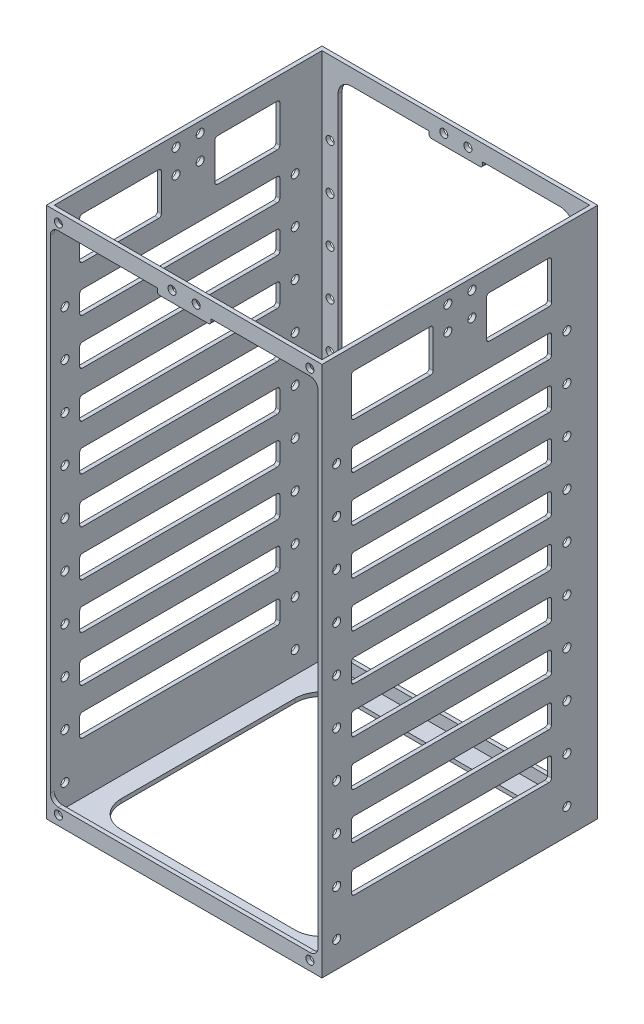
SolidWorks part; units mm, degrees
ref_plane "Front Plane" through (0, 0, 0) normal (0, 0, 1) x (1, 0, 0)
ref_plane "Top Plane" through (0, 0, 0) normal (0, 1, 0) x (1, 0, 0)
ref_plane "Right Plane" through (0, 0, 0) normal (1, 0, 0) x (0, 0, -1)
sketch "Sketch1" plane through (0, 0, 0) normal (0, 1, 0) x (1, 0, 0)
  line L1 (-51.5, -51.5) -> (51.5, -51.5)
  line L2 (-51.5, -51.5) -> (-51.5, 51.5)
  line L3 (-51.5, 51.5) -> (51.5, 51.5)
  line L4 (51.5, -51.5) -> (51.5, 51.5)
  line L5 (-51.5, -51.5) -> (51.5, 51.5) construction
  line L6 (-51.5, 51.5) -> (51.5, -51.5) construction
  line L7 (-32.5, -42.5) -> (32.5, -42.5)
  line L8 (-42.5, -32.5) -> (-42.5, 32.5)
  line L9 (-32.5, 42.5) -> (32.5, 42.5)
  line L10 (42.5, -32.5) -> (42.5, 32.5)
  line L11 (-42.5, -42.5) -> (42.5, 42.5) construction
  line L12 (-42.5, 42.5) -> (42.5, -42.5) construction
  arc A0 (32.5, -42.5) -> (42.5, -32.5) centre (32.5, -32.5) ccw
  arc A1 (32.5, 42.5) -> (42.5, 32.5) centre (32.5, 32.5) cw
  arc A2 (-42.5, 32.5) -> (-32.5, 42.5) centre (-32.5, 32.5) cw
  arc A3 (-32.5, -42.5) -> (-42.5, -32.5) centre (-32.5, -32.5) cw
  point P0 (0, 0)
  point P6 (0, 0)
  dimension "D3" = 10
  dimension "D1" = 103
  dimension "D2" = 42.5
extrude "Boss-Extrude2" add sketch "Sketch1" along normal blind 1.5 contours A3 L7 A0 L10 A1 L9 A2 L8 | L2 L1 L4 L3 region at (0, 0, 0)
sketch "Sketch3" plane through (0, 1.5, 0) normal (0, 1, 0) x (1, 0, 0)
  line L1 (-51.5, -51.5) -> (51.5, -51.5)
  line L2 (-51.5, -51.5) -> (-51.5, 51.5)
  line L3 (-51.5, 51.5) -> (51.5, 51.5)
  line L4 (51.5, -51.5) -> (51.5, 51.5)
  line L5 (-51.5, -51.5) -> (51.5, 51.5) construction
  line L6 (-51.5, 51.5) -> (51.5, -51.5) construction
  line L7 (-50, -50) -> (50, -50)
  line L8 (-50, -50) -> (-50, 50)
  line L9 (-50, 50) -> (50, 50)
  line L10 (50, -50) -> (50, 50)
  line L11 (-50, -50) -> (50, 50) construction
  line L12 (-50, 50) -> (50, -50) construction
  point P0 (0, 0)
  point P7 (0, 0)
  dimension "D1" = 100
extrude "Boss-Extrude3" add sketch "Sketch3" along normal blind 197 contours L8 L7 L10 L9 | L2 L3 L4 L1
sketch "Sketch4" plane through (0, 0, -51.5) normal (0, 0, 1) x (1, 0, 0)
  line L0 (-51.5, 0) -> (51.5, 0) construction
  line L1 (-39, 6) -> (39, 6)
  line L2 (-44, 11) -> (-44, 187.5)
  line L3 (-39, 192.5) -> (39, 192.5)
  line L4 (44, 11) -> (44, 187.5)
  line L5 (-44, 6) -> (44, 192.5) construction
  line L6 (-44, 192.5) -> (44, 6) construction
  line L7 (51.5, 198.5) -> (51.5, 0) construction
  line L8 (-50, 198.5) -> (50, 198.5) construction
  line L9 (-51.5, 198.5) -> (-51.5, 0) construction
  arc A0 (-39, 6) -> (-44, 11) centre (-39, 11) cw
  arc A1 (39, 6) -> (44, 11) centre (39, 11) ccw
  arc A2 (39, 192.5) -> (44, 187.5) centre (39, 187.5) cw
  arc A3 (-44, 187.5) -> (-39, 192.5) centre (-39, 187.5) cw
  point P0 (0, 99.25)
  dimension "D5" = 5
  dimension "D1" = 6
  dimension "D2" = 7.5
  dimension "D3" = 6
  dimension "D4" = 7.5
extrude "Cut-Extrude1" cut sketch "Sketch4" along normal up to surface (1.5 mm away) up to face at (0, 100, -50)
sketch "Sketch5" plane through (0, 0, 51.5) normal (0, 0, 1) x (1, 0, 0)
  line L0 (-51.5, 198.5) -> (51.5, 198.5) construction
  line L1 (-47, 6) -> (47, 6)
  line L2 (-50, 9) -> (-50, 189.5)
  line L3 (-47, 192.5) -> (47, 192.5)
  line L4 (50, 9) -> (50, 189.5)
  line L5 (-50, 6) -> (50, 192.5) construction
  line L6 (-50, 192.5) -> (50, 6) construction
  line L7 (-51.5, 1.5) -> (51.5, 1.5) construction
  line L8 (-51.5, 198.5) -> (-51.5, 0) construction
  line L9 (51.5, 198.5) -> (51.5, 0) construction
  arc A0 (47, 6) -> (50, 9) centre (47, 9) ccw
  arc A1 (-47, 6) -> (-50, 9) centre (-47, 9) cw
  arc A2 (47, 192.5) -> (50, 189.5) centre (47, 189.5) cw
  arc A3 (-50, 189.5) -> (-47, 192.5) centre (-47, 189.5) cw
  point P0 (0, 99.25)
  dimension "D5" = 3
  dimension "D1" = 6
  dimension "D2" = 4.5
  dimension "D3" = 1.5
  dimension "D4" = 1.5
sketch "Sketch6" plane through (51.5, 0, 0) normal (1, 0, 0) x (0, 0, -1)
  line L0 (-51.5, 6) -> (-51.5, 192.5) construction
  line L2 (-51.5, 0) -> (51.5, 0) construction
  circle A0 centre (-46, 9.75) radius 1.5
  circle A1 centre (40, 9.75) radius 1.5
  circle A2 centre (-46, 26.85) radius 1.5
  circle A3 centre (40, 26.85) radius 1.5
  circle A4 centre (-46, 43.95) radius 1.5
  circle A5 centre (40, 43.95) radius 1.5
  circle A6 centre (-46, 61.05) radius 1.5
  circle A7 centre (40, 61.05) radius 1.5
  circle A8 centre (-46, 78.15) radius 1.5
  circle A9 centre (40, 78.15) radius 1.5
  circle A10 centre (-46, 95.25) radius 1.5
  circle A11 centre (40, 95.25) radius 1.5
  circle A12 centre (-46, 112.35) radius 1.5
  circle A13 centre (40, 112.35) radius 1.5
  circle A14 centre (-46, 129.45) radius 1.5
  circle A15 centre (40, 129.45) radius 1.5
  circle A16 centre (-46, 146.55) radius 1.5
  circle A17 centre (40, 146.55) radius 1.5
  circle A18 centre (-46, 163.65) radius 1.5
  circle A19 centre (40, 163.65) radius 1.5
  dimension "D4" = 3
  dimension "D5" = 3
  dimension "D1" = 5.5
  dimension "D2" = 86
  dimension "D3" = 9.75
  dimension "D7" = 17.1
  dimension "D9" = 17.1
  dimension "D6" = 9
  dimension "D8" = 2
extrude "Cut-Extrude2" cut sketch "Sketch6" against normal through all
extrude "Cut-Extrude3" cut sketch "Sketch5" against normal up to surface (1.5 mm away) up to face at (0, 100, 50)
sketch "Sketch7" plane through (51.5, 0, 0) normal (1, 0, 0) x (0, 0, -1)
  line L0 (-40.5, 38.95) -> (-40.5, 45.45)
  line L1 (-39.5, 20.85) -> (33.25, 20.85)
  line L2 (-40.5, 21.85) -> (-40.5, 28.35)
  line L3 (-39.5, 29.35) -> (33.25, 29.35)
  line L4 (34.25, 21.85) -> (34.25, 28.35)
  line L5 (-40.5, 20.85) -> (34.25, 29.35) construction
  line L6 (-40.5, 29.35) -> (34.25, 20.85) construction
  line L7 (-40.5, 158.65) -> (-40.5, 165.15)
  line L8 (-39.5, 37.95) -> (33.25, 37.95)
  line L9 (34.25, 38.95) -> (34.25, 45.45)
  line L10 (-39.5, 46.45) -> (33.25, 46.45)
  line L11 (-40.5, 56.05) -> (-40.5, 62.55)
  line L12 (-39.5, 55.05) -> (33.25, 55.05)
  line L13 (34.25, 56.05) -> (34.25, 62.55)
  line L14 (-39.5, 63.55) -> (33.25, 63.55)
  line L15 (-40.5, 73.15) -> (-40.5, 79.65)
  line L16 (-39.5, 72.15) -> (33.25, 72.15)
  line L17 (34.25, 73.15) -> (34.25, 79.65)
  line L18 (-39.5, 80.65) -> (33.25, 80.65)
  line L19 (-40.5, 90.25) -> (-40.5, 96.75)
  line L20 (-39.5, 89.25) -> (33.25, 89.25)
  line L21 (34.25, 90.25) -> (34.25, 96.75)
  line L22 (-39.5, 97.75) -> (33.25, 97.75)
  line L23 (-40.5, 107.35) -> (-40.5, 113.85)
  line L24 (-39.5, 106.35) -> (33.25, 106.35)
  line L25 (34.25, 107.35) -> (34.25, 113.85)
  line L26 (-39.5, 114.85) -> (33.25, 114.85)
  line L27 (-40.5, 124.45) -> (-40.5, 130.95)
  line L28 (-39.5, 123.45) -> (33.25, 123.45)
  line L29 (34.25, 124.45) -> (34.25, 130.95)
  line L30 (-39.5, 131.95) -> (33.25, 131.95)
  line L31 (-40.5, 141.55) -> (-40.5, 148.05)
  line L32 (-39.5, 140.55) -> (33.25, 140.55)
  line L33 (34.25, 141.55) -> (34.25, 148.05)
  line L34 (-39.5, 149.05) -> (33.25, 149.05)
  line L35 (-39.5, 157.65) -> (33.25, 157.65)
  line L36 (34.25, 158.65) -> (34.25, 165.15)
  line L37 (-39.5, 166.15) -> (33.25, 166.15)
  line L38 (-40.5, 141.55) -> (-40.5, 158.65) construction
  circle A0 centre (-46, 9.75) radius 1.5 construction
  arc A1 (33.25, 29.35) -> (34.25, 28.35) centre (33.25, 28.35) cw
  arc A2 (33.25, 20.85) -> (34.25, 21.85) centre (33.25, 21.85) ccw
  arc A3 (-39.5, 20.85) -> (-40.5, 21.85) centre (-39.5, 21.85) cw
  arc A4 (-40.5, 28.35) -> (-39.5, 29.35) centre (-39.5, 28.35) cw
  arc A5 (-40.5, 45.45) -> (-39.5, 46.45) centre (-39.5, 45.45) cw
  arc A6 (-39.5, 37.95) -> (-40.5, 38.95) centre (-39.5, 38.95) cw
  arc A7 (33.25, 37.95) -> (34.25, 38.95) centre (33.25, 38.95) ccw
  arc A8 (33.25, 46.45) -> (34.25, 45.45) centre (33.25, 45.45) cw
  arc A9 (-40.5, 62.55) -> (-39.5, 63.55) centre (-39.5, 62.55) cw
  arc A10 (-39.5, 55.05) -> (-40.5, 56.05) centre (-39.5, 56.05) cw
  arc A11 (33.25, 55.05) -> (34.25, 56.05) centre (33.25, 56.05) ccw
  arc A12 (33.25, 63.55) -> (34.25, 62.55) centre (33.25, 62.55) cw
  arc A13 (-40.5, 79.65) -> (-39.5, 80.65) centre (-39.5, 79.65) cw
  arc A14 (-39.5, 72.15) -> (-40.5, 73.15) centre (-39.5, 73.15) cw
  arc A15 (33.25, 72.15) -> (34.25, 73.15) centre (33.25, 73.15) ccw
  arc A16 (33.25, 80.65) -> (34.25, 79.65) centre (33.25, 79.65) cw
  arc A17 (-40.5, 96.75) -> (-39.5, 97.75) centre (-39.5, 96.75) cw
  arc A18 (-39.5, 89.25) -> (-40.5, 90.25) centre (-39.5, 90.25) cw
  arc A19 (33.25, 89.25) -> (34.25, 90.25) centre (33.25, 90.25) ccw
  arc A20 (33.25, 97.75) -> (34.25, 96.75) centre (33.25, 96.75) cw
  arc A21 (-40.5, 113.85) -> (-39.5, 114.85) centre (-39.5, 113.85) cw
  arc A22 (-39.5, 106.35) -> (-40.5, 107.35) centre (-39.5, 107.35) cw
  arc A23 (33.25, 106.35) -> (34.25, 107.35) centre (33.25, 107.35) ccw
  arc A24 (33.25, 114.85) -> (34.25, 113.85) centre (33.25, 113.85) cw
  arc A25 (-40.5, 130.95) -> (-39.5, 131.95) centre (-39.5, 130.95) cw
  arc A26 (-39.5, 123.45) -> (-40.5, 124.45) centre (-39.5, 124.45) cw
  arc A27 (33.25, 123.45) -> (34.25, 124.45) centre (33.25, 124.45) ccw
  arc A28 (33.25, 131.95) -> (34.25, 130.95) centre (33.25, 130.95) cw
  arc A29 (-40.5, 148.05) -> (-39.5, 149.05) centre (-39.5, 148.05) cw
  arc A30 (-39.5, 140.55) -> (-40.5, 141.55) centre (-39.5, 141.55) cw
  arc A31 (33.25, 140.55) -> (34.25, 141.55) centre (33.25, 141.55) ccw
  arc A32 (33.25, 149.05) -> (34.25, 148.05) centre (33.25, 148.05) cw
  arc A33 (-40.5, 165.15) -> (-39.5, 166.15) centre (-39.5, 165.15) cw
  arc A34 (-39.5, 157.65) -> (-40.5, 158.65) centre (-39.5, 158.65) cw
  circle A35 centre (40, 9.75) radius 1.5 construction
  arc A36 (33.25, 157.65) -> (34.25, 158.65) centre (33.25, 158.65) ccw
  arc A37 (33.25, 166.15) -> (34.25, 165.15) centre (33.25, 165.15) cw
  point P0 (-3.125, 25.1)
  dimension "D5" = 1
  dimension "D3" = 5.75
  dimension "D1" = 8.5
  dimension "D2" = 11.1
  dimension "D4" = 5.5
  dimension "D7" = 8.6
  dimension "D9" = 8.6
  dimension "D6" = 8
  dimension "D8" = 2
extrude "Cut-Extrude4" cut sketch "Sketch7" against normal through all
sketch "Sketch8" plane through (51.5, 0, 0) normal (1, 0, 0) x (0, 0, -1)
  line L7 (-51.5, 198.5) -> (51.5, 198.5) construction
  line L15 (-39.5, 190.5) -> (33.25, 190.5)
  line L16 (-40.5, 189.5) -> (-40.5, 175.75)
  line L17 (-39.5, 174.75) -> (33.25, 174.75)
  line L18 (34.25, 189.5) -> (34.25, 175.75)
  line L19 (33.25, 166.15) -> (-39.5, 166.15) construction
  arc A15 (33.25, 190.5) -> (34.25, 189.5) centre (33.25, 189.5) cw
  arc A16 (33.25, 174.75) -> (34.25, 175.75) centre (33.25, 175.75) ccw
  arc A17 (-40.5, 175.75) -> (-39.5, 174.75) centre (-39.5, 175.75) ccw
  arc A18 (-39.5, 190.5) -> (-40.5, 189.5) centre (-39.5, 189.5) ccw
  circle A19 centre (-46, 163.65) radius 1.5 construction
  circle A20 centre (40, 163.65) radius 1.5 construction
  point P0 (-2.625, 162.85)
  dimension "D6" = 1
  dimension "D2" = 8.6
  dimension "D8" = 8
  dimension "D9" = 5.5
  dimension "D10" = 5.75
extrude "Cut-Extrude5" cut sketch "Sketch8" against normal through all
sketch "Sketch15" plane through (51.5, 0, 0) normal (1, 0, 0) x (0, 0, -1)
  line L0 (-50, 198.5) -> (-50, 189.5) construction
  line L7 (33.25, 190.5) -> (-39.5, 190.5) construction
  line L8 (-10, 190.5) -> (10, 190.5)
  line L9 (-10, 190.5) -> (-10, 174.75)
  line L10 (-10, 174.75) -> (10, 174.75)
  line L11 (10, 190.5) -> (10, 174.75)
  line L12 (-39.5, 174.75) -> (33.25, 174.75) construction
  dimension "D1" = 20
  dimension "D2" = 40
extrude "Boss-Extrude4" add sketch "Sketch15" against normal up to surface (1.5 mm away) up to face at (50, 182.625, 3.125)
sketch "Sketch16" plane through (-51.5, 0, 0) normal (-1, 0, 0) x (0, 0, 1)
  line L7 (-10, 190.5) -> (10, 190.5)
  line L8 (-10, 190.5) -> (-10, 174.75)
  line L9 (-10, 174.75) -> (10, 174.75)
  line L10 (10, 190.5) -> (10, 174.75)
extrude "Boss-Extrude5" add sketch "Sketch16" against normal up to surface (1.5 mm away) up to face at (-50, 182.625, 3.125)
sketch "Sketch9" plane through (51.5, 0, 0) normal (1, 0, 0) x (0, 0, -1)
  line L0 (-51.5, 198.5) -> (51.5, 198.5) construction
  line L2 (-11.0428, 190) -> (9.2919, 190) construction
  line L3 (-50, 198.5) -> (-50, 189.5) construction
  circle A0 centre (-4.5, 194.5) radius 1.5
  circle A1 centre (4.5, 194.5) radius 1.5
  circle A2 centre (4.5, 185.5) radius 1.5
  circle A3 centre (-4.5, 185.5) radius 1.5
  dimension "D1" = 3
  dimension "D3" = 9
  dimension "D5" = 3
  dimension "D2" = 4
  dimension "D4" = 45.5
  dimension "D6" = 4.5
extrude "Cut-Extrude6" cut sketch "Sketch9" against normal through all
fillet "Fillet1" radius 1 8 edges at (-50.75, 174.75, 10) (-50.75, 190.5, 10) (-50.75, 190.5, -10) (-50.75, 174.75, -10) (50.75, 190.5, 10) (50.75, 174.75, 10) (50.75, 174.75, -10) (50.75, 190.5, -10)
sketch "Sketch18" plane through (0, 0, -51.5) normal (0, 0, -1) x (-1, 0, 0)
  line L0 (-39, 192.5) -> (39, 192.5) construction
  line L1 (-10, 192.5) -> (10, 192.5)
  line L2 (-10, 192.5) -> (-10, 191.5)
  line L3 (-9, 190.5) -> (9, 190.5)
  line L4 (10, 192.5) -> (10, 191.5)
  line L6 (-50, 198.5) -> (-50, 1.5) construction
  arc A0 (9, 190.5) -> (10, 191.5) centre (9, 191.5) ccw
  arc A1 (-10, 191.5) -> (-9, 190.5) centre (-9, 191.5) ccw
  point P4 (-10, 192)
  dimension "D3" = 1
  dimension "D1" = 2
  dimension "D2" = 20
  dimension "D4" = 40
extrude "Boss-Extrude7" add sketch "Sketch18" against normal up to surface (1.5 mm away) up to face at (0, 99.25, -50)
sketch "Sketch17" plane through (0, 0, 51.5) normal (0, 0, 1) x (1, 0, 0)
  line L0 (47, 192.5) -> (-47, 192.5) construction
  line L1 (-10, 192.5) -> (10, 192.5)
  line L2 (-10, 192.5) -> (-10, 191.5)
  line L3 (-9, 190.5) -> (9, 190.5)
  line L4 (10, 192.5) -> (10, 191.5)
  line L6 (-50, 189.5) -> (-50, 9) construction
  arc A0 (9, 190.5) -> (10, 191.5) centre (9, 191.5) ccw
  arc A1 (-10, 191.5) -> (-9, 190.5) centre (-9, 191.5) ccw
  dimension "D4" = 1
  dimension "D1" = 20
  dimension "D2" = 40
  dimension "D3" = 2
extrude "Boss-Extrude6" add sketch "Sketch17" against normal up to surface (1.5 mm away) up to face at (0, 193.7071, 50)
sketch "Sketch19" plane through (0, 0, 51.5) normal (0, 0, 1) x (1, 0, 0)
  line L0 (0, 198.5) -> (0, 190.5) construction
  line L1 (-9, 190.5) -> (9, 190.5) construction
  line L3 (-51.5, 198.5) -> (51.5, 198.5) construction
  circle A0 centre (-4.5, 194.5) radius 1.5
  circle A1 centre (4.5, 194.5) radius 1.5
  dimension "D1" = 3
  dimension "D2" = 4
  dimension "D3" = 4.5
extrude "Cut-Extrude7" cut sketch "Sketch19" against normal through all
sketch "Sketch20" plane through (0, 0, 51.5) normal (0, 0, 1) x (1, 0, 0)
  line L1 (-51.5, 0) -> (51.5, 0) construction
  line L2 (0, 198.5) -> (0, 0) construction
  line L3 (-51.5, 198.5) -> (51.5, 198.5) construction
  line L4 (-50, 198.5) -> (-50, 189.5) construction
  line L5 (-50, 9) -> (-50, 1.5) construction
  circle A0 centre (-46.98, 3.5) radius 1.5
  circle A1 centre (-46.98, 195) radius 1.5
  circle A2 centre (46.98, 3.5) radius 1.5
  circle A3 centre (46.98, 195) radius 1.5
  dimension "D1" = 3
  dimension "D4" = 3
  dimension "D2" = 3.02
  dimension "D3" = 3.5
  dimension "D5" = 3.02
  dimension "D6" = 3.5
extrude "Cut-Extrude8" cut sketch "Sketch20" against normal up to surface (1.5 mm away) up to face at (-6, 194.5, 50)
sketch "Sketch23" plane through (0, 0, -51.5) normal (0, 0, -1) x (-1, 0, 0)
  line L0 (-51.5, 198.5) -> (-51.5, 0) construction
  line L1 (51.5, 0) -> (-51.5, 0) construction
  line L2 (0, 198.5) -> (0, 0) construction
  line L3 (51.5, 198.5) -> (-51.5, 198.5) construction
  circle A0 centre (-47, 17.05) radius 1.5
  circle A2 centre (-47, 34.15) radius 1.5
  circle A3 centre (-47, 51.25) radius 1.5
  circle A4 centre (-47, 68.35) radius 1.5
  circle A5 centre (-47, 85.45) radius 1.5
  circle A6 centre (-47, 102.55) radius 1.5
  circle A7 centre (-47, 119.65) radius 1.5
  circle A8 centre (-47, 136.75) radius 1.5
  circle A9 centre (-47, 153.85) radius 1.5
  circle A10 centre (-47, 170.95) radius 1.5
  circle A11 centre (47, 170.95) radius 1.5
  circle A12 centre (47, 153.85) radius 1.5
  circle A13 centre (47, 136.75) radius 1.5
  circle A14 centre (47, 119.65) radius 1.5
  circle A15 centre (47, 102.55) radius 1.5
  circle A16 centre (47, 85.45) radius 1.5
  circle A17 centre (47, 68.35) radius 1.5
  circle A18 centre (47, 51.25) radius 1.5
  circle A19 centre (47, 34.15) radius 1.5
  circle A20 centre (47, 17.05) radius 1.5
  dimension "D1" = 3
  dimension "D2" = 4.5
  dimension "D3" = 17.05
  dimension "D5" = 17.1
  dimension "D4" = 10
extrude "Cut-Extrude10" cut sketch "Sketch23" against normal up to surface (1.5 mm away) up to face at (-6, 194.5, -50)
